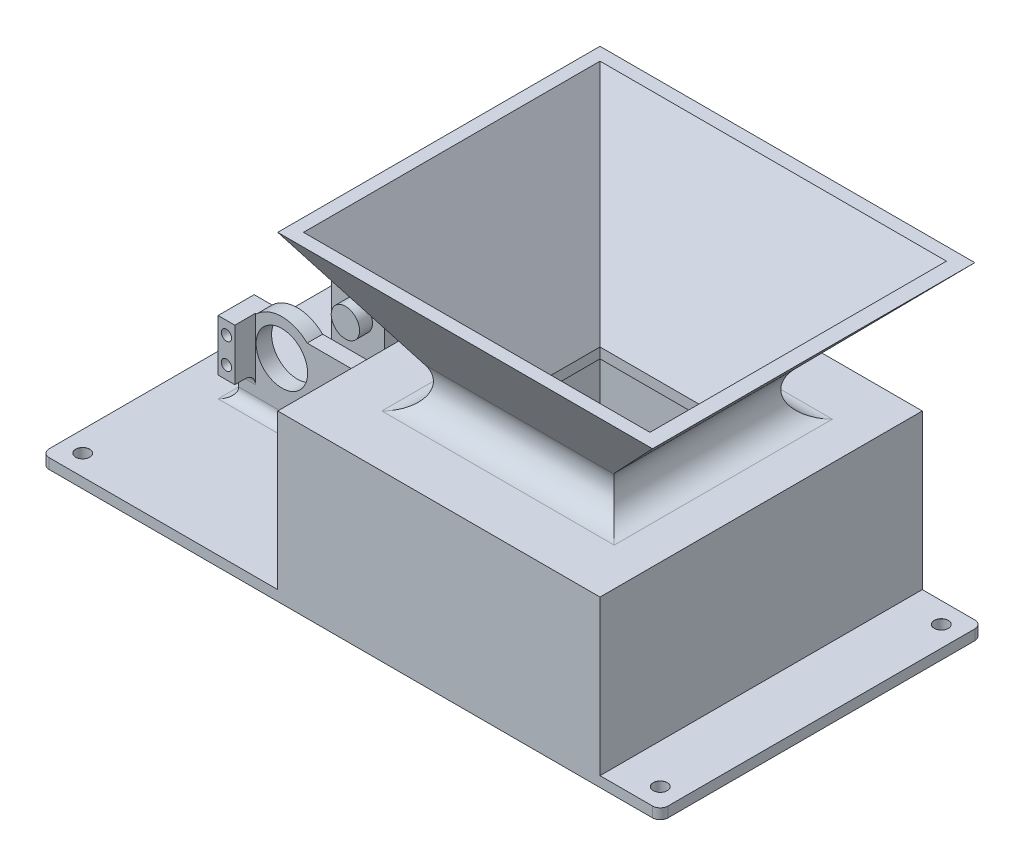
SolidWorks part; units mm, degrees
note: The reader was unsure of these and kept them because the rebuilt part matched: shared geometry of "草图13<2>".
ref_plane "前视基准面" through (0, 0, 0) normal (0, 0, 1) x (1, 0, 0)
ref_plane "上视基准面" through (0, 0, 0) normal (0, 1, 0) x (1, 0, 0)
ref_plane "右视基准面" through (0, 0, 0) normal (1, 0, 0) x (0, 0, -1)
other "Configuration Table"
sketch "草图1" plane through (0, 0, 0) normal (0, 1, 0) x (1, 0, 0)
  line L1 (-120, -62.5) -> (120, -62.5)
  line L2 (-120, -62.5) -> (-120, 62.5)
  line L3 (-120, 62.5) -> (120, 62.5)
  line L4 (120, -62.5) -> (120, 62.5)
  line L5 (-120, -62.5) -> (120, 62.5) construction
  line L6 (-120, 62.5) -> (120, -62.5) construction
  point P0 (0, 0)
  dimension "D1" = 240
  dimension "D2" = 125
extrude "凸台-拉伸1" add sketch "草图1" along normal blind 4
sketch "草图2" plane through (0, 4, 0) normal (0, 1, 0) x (1, 0, 0)
  line L0 (-120, 0) -> (120, 0) construction
  line L1 (-120, 62.5) -> (-120, -62.5) construction
  line L2 (120, -62.5) -> (120, 62.5) construction
  line L3 (0, 62.5) -> (0, -62.5) construction
  line L4 (120, 62.5) -> (-120, 62.5) construction
  line L5 (-120, -62.5) -> (120, -62.5) construction
  point P12 (-112, 54.5)
  point P13 (-112, -54.5)
  point P14 (112, -54.5)
  point P15 (112, 54.5)
  dimension "D1" = 8
  dimension "D2" = 8
hole_wizard "Ø5.4 (5.4) 直径孔1" positions "草图2" profile "草图3" hole size "Ø5.4" standard "GB" end condition through all
sketch "草图3" plane through (112, 4, -54.5) normal (1, 0, 0) x (0, 0, 1)
  line L0 (0, 0) -> (0, 4)
  line L1 (0, 4) -> (2.7, 4)
  line L2 (2.7, 4) -> (2.7, 0.025)
  line L3 (2.7, 0.025) -> (2.725, 0)
  line L5 (2.725, 0) -> (0, 0)
  line L6 (-2.7, 0.025) -> (-2.725, 0) construction
  line L11 (0, -6.35) -> (0, 107.95) construction
  dimension "通孔孔直径" = 5.4
  dimension "通孔孔深度" = 4
  dimension "近端锥形沉头孔直径" = 5.45
  dimension "近端锥形沉头孔角度" = 90
fillet "圆角1" radius 3 4 edges at (120, 2, 62.5) (120, 2, -62.5) (-120, 2, 62.5) (-120, 2, -62.5)
sketch "草图4" plane through (0, 0, 0) normal (0, 0, 1) x (1, 0, 0)
  line L0 (-117, 4) -> (117, 4) construction
  line L1 (-100, 4) -> (-46, 4)
  line L2 (-100, 4) -> (-100, 36)
  line L3 (-100, 36) -> (-93.048, 36)
  line L4 (-46, 4) -> (-46, 36)
  line L5 (-120, 0) -> (-120, 4) construction
  line L7 (-73, 4) -> (-73, 36) construction
  line L9 (-83.25, 36) -> (-83.25, 4) construction
  line L10 (-100, 26) -> (-46, 26) construction
  line L12 (-73.452, 36) -> (-46, 36)
  arc A1 (-73.452, 36) -> (-93.048, 36) centre (-83.25, 26) ccw
  circle A2 centre (-83.25, 26) radius 10
  dimension "D1" = 54
  dimension "D2" = 32
  dimension "D3" = 20
extrude "凸台-拉伸2" add sketch "草图4" along normal blind 6
sketch "草图6" plane through (0, 0, 6) normal (0, 0, 1) x (1, 0, 0)
  line L0 (-100, 16) -> (-46, 16) construction
  line L1 (-100, 36) -> (-100, 4) construction
  line L2 (-46, 4) -> (-46, 36) construction
  line L3 (-100, 4) -> (-46, 4) construction
  line L4 (-73, 4) -> (-73, 36) construction
  line L5 (-46, 36) -> (-73.452, 36) construction
  line L6 (-100, 36) -> (-100, 16)
  line L7 (-93.048, 36) -> (-100, 36) construction
  line L8 (-100, 16) -> (-93.5, 16)
  line L9 (-93.5, 16) -> (-93.5, 36)
  line L10 (-93.5, 36) -> (-100, 36)
  line L11 (-52.5, 16) -> (-52.5, 36)
  line L12 (-46, 16) -> (-52.5, 16)
  line L13 (-46, 36) -> (-46, 16)
  line L14 (-52.5, 36) -> (-46, 36)
  dimension "D1" = 12
  dimension "D2" = 6.5
extrude "凸台-拉伸3" add sketch "草图6" along normal blind 8
sketch "草图7" plane through (0, 0, 14) normal (0, 0, 1) x (1, 0, 0)
  line L0 (-73, 4) -> (-73, 36) construction
  line L1 (-100, 4) -> (-46, 4) construction
  line L2 (-52.5, 36) -> (-73.452, 36) construction
  line L3 (-96.75, 16) -> (-96.75, 36) construction
  line L4 (-100, 16) -> (-93.5, 16) construction
  line L5 (-93.5, 36) -> (-100, 36) construction
  line L6 (-100, 26) -> (-93.5, 26) construction
  line L7 (-100, 36) -> (-100, 16) construction
  line L8 (-93.5, 16) -> (-93.5, 36) construction
  circle A0 centre (-96.75, 31) radius 2
  circle A1 centre (-96.75, 21) radius 2
  circle A2 centre (-49.25, 21) radius 2
  circle A3 centre (-49.25, 31) radius 2
  dimension "D1" = 4
  dimension "D2" = 5
extrude "切除-拉伸1" cut sketch "草图7" against normal up to surface (14 mm away) up to face at (-76.4167, 26, 0)
fillet "圆角2" radius 4 2 edges at (-49.25, 16, 6) (-96.75, 16, 6)
fillet "圆角3" radius 4 1 edges at (-73, 4, 6)
fillet "圆角4" radius 4 3 edges at (-73, 4, 0) (-100, 4, 5) (-46, 4, 5)
sketch "草图8" plane through (0, 0, 0) normal (0, 0, -1) x (-1, 0, 0)
  line L0 (73, 8) -> (73, 36)
  line L1 (46, 8) -> (100, 8) construction
  line L2 (46, 36) -> (73.452, 36) construction
  line L3 (93.5, 36) -> (93.5, 8)
  line L4 (93.048, 36) -> (100, 36) construction
  line L5 (100, 36) -> (100, 8) construction
  line L6 (73, 8) -> (73, 4)
  line L7 (104, 4) -> (42, 4) construction
  line L8 (73, 4) -> (93.5, 4)
  line L9 (93.5, 4) -> (93.5, 8)
  arc A0 (73, 36) -> (93.5, 36) centre (83.25, 24.8672) cw
  dimension "D1" = 6.5
extrude "凸台-拉伸4" add sketch "草图8" along normal blind 8 from offset 23.5
sketch "草图9" plane through (0, 0, -23.5) normal (0, 0, 1) x (1, 0, 0)
  circle A0 centre (-83.1168, 25.813) radius 5.5
  dimension "D1" = 11
extrude "凸台-拉伸5" add sketch "草图9" along normal blind 5
fillet "圆角5" radius 4 1 edges at (-83.25, 4, -31.5)
fillet "圆角6" radius 4 3 edges at (-73, 4, -29.5) (-83.25, 4, -23.5) (-93.5, 4, -29.5)
sketch "草图10" plane through (0, 4, 0) normal (0, 1, 0) x (1, 0, 0)
  line L0 (117, 62.5) -> (-117, 62.5) construction
  line L1 (-117, -62.5) -> (117, -62.5) construction
  line L2 (-28.367, 62.5) -> (96.633, 62.5)
  line L3 (-28.367, 62.5) -> (-28.367, -62.5)
  line L4 (-28.367, -62.5) -> (96.633, -62.5)
  line L5 (96.633, 62.5) -> (96.633, -62.5)
  line L6 (-28.367, 0) -> (96.633, 0) construction
  line L7 (34.133, 62.5) -> (34.133, -62.5) construction
  line L9 (-23.367, -57.5) -> (91.633, -57.5)
  line L10 (-23.367, -57.5) -> (-23.367, 57.5)
  line L11 (-23.367, 57.5) -> (91.633, 57.5)
  line L12 (91.633, -57.5) -> (91.633, 57.5)
  line L13 (-23.367, -57.5) -> (91.633, 57.5) construction
  line L14 (-23.367, 57.5) -> (91.633, -57.5) construction
  point P12 (34.133, 0)
  dimension "D1" = 5
ref_plane "基准面1" through (0, 64, 0) normal (0, 1, 0) x (1, 0, 0)
sketch "草图11" plane through (0, 64, 0) normal (0, 1, 0) x (1, 0, 0)
  line L0 (-23.367, -57.5) -> (91.633, 57.5) construction
  line L1 (10.133, -24) -> (58.133, -24)
  line L2 (10.133, -24) -> (10.133, 24)
  line L3 (10.133, 24) -> (58.133, 24)
  line L4 (58.133, -24) -> (58.133, 24)
  line L5 (10.133, -24) -> (15.133, -19) construction
  line L6 (10.133, 24) -> (15.133, 19) construction
  line L7 (53.133, -19) -> (58.133, -24) construction
  line L8 (53.133, 19) -> (58.133, 24) construction
  point P0 (34.133, 0)
  point P8 (34.133, 0)
  dimension "D1" = 48
extrude "凸台-拉伸6" add sketch "草图10" along normal blind 60
sketch "草图12" plane through (0, 0, -57.5) normal (0, 0, 1) x (1, 0, 0)
  line L1 (-23.367, 64) -> (91.633, 64)
  line L2 (-23.367, 64) -> (-23.367, 60)
  line L3 (-23.367, 60) -> (91.633, 60)
  line L4 (91.633, 64) -> (91.633, 60)
  dimension "D1" = 4
  dimension "D2" = 115
extrude "凸台-拉伸7" add sketch "草图12" along normal blind 115
sketch "草图13" plane through (0, 64, 0) normal (0, 1, 0) x (1, 0, 0)
  line L0 (-28.367, 0) -> (96.633, 0) construction
  line L1 (-28.367, 62.5) -> (-28.367, -62.5) construction
  line L2 (96.633, -62.5) -> (96.633, 62.5) construction
  line L3 (34.133, -62.5) -> (34.133, 62.5) construction
  line L4 (-28.367, -62.5) -> (96.633, -62.5) construction
  line L5 (96.633, 62.5) -> (-28.367, 62.5) construction
  line L6 (-28.367, -62.5) -> (96.633, 62.5) construction
  line L8 (12.633, -21.5) -> (55.633, -21.5)
  line L9 (12.633, -21.5) -> (12.633, 21.5)
  line L10 (12.633, 21.5) -> (55.633, 21.5)
  line L11 (55.633, -21.5) -> (55.633, 21.5)
  line L12 (12.633, -21.5) -> (55.633, 21.5) construction
  line L13 (12.633, 21.5) -> (55.633, -21.5) construction
  point P16 (34.133, 0)
  dimension "D1" = 43
extrude "切除-拉伸3" cut sketch "草图13" against normal up to next
ref_plane "基准面2" through (0, 124, 0) normal (0, 1, 0) x (1, 0, 0)
sketch "草图14" plane through (0, 124, 0) normal (0, 1, 0) x (1, 0, 0)
  line L0 (96.633, -62.5) -> (117, -62.5) construction
  line L1 (-28.367, 62.5) -> (117, 62.5)
  line L2 (-28.367, 62.5) -> (-28.367, -62.5)
  line L3 (-28.367, -62.5) -> (117, -62.5)
  line L4 (117, 62.5) -> (117, -62.5)
  arc A0 (117, -62.5) -> (120, -59.5) centre (117, -59.5) ccw construction
loft "放样1" add profiles "草图14", "草图11"
sketch "草图15" plane through (0, 124, 0) normal (0, 1, 0) x (1, 0, 0)
  line L0 (117, 62.5) -> (-28.367, 62.5) construction
  line L1 (-23.367, 57.5) -> (111, 57.5)
  line L2 (-23.367, 57.5) -> (-23.367, -57.5)
  line L3 (-23.367, -57.5) -> (111, -57.5)
  line L4 (111, 57.5) -> (111, -57.5)
  line L5 (-28.367, 62.5) -> (-28.367, -62.5) construction
  line L6 (-28.367, -62.5) -> (117, -62.5) construction
  line L7 (117, -62.5) -> (117, 62.5) construction
  dimension "D1" = 5
  dimension "D2" = 5
  dimension "D3" = 5
  dimension "D4" = 6
loft "切除-放样5" cut profiles "草图15", "草图13<2>"
sketch "草图13<2>" plane through (0, 64, 0) normal (0, 1, 0) x (1, 0, 0) same geometry as "草图13"
ref_plane "基准面3" through (-28.367, 124, -62.5) normal (0, 0, 1) x (1, 0, 0)
fillet "圆角7" radius 10 4 edges
